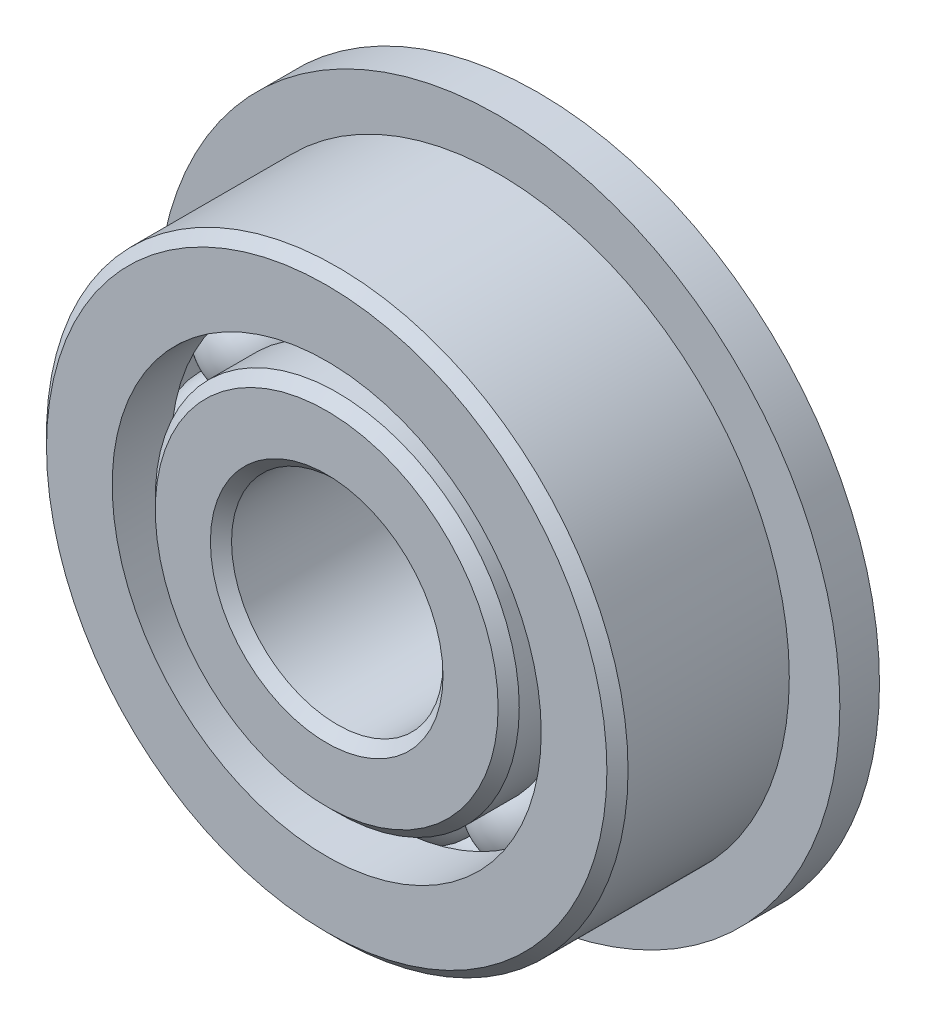
SolidWorks part; units mm, degrees
ref_plane "Front Plane" through (0, 0, 0) normal (0, 0, 1) x (1, 0, 0)
ref_plane "Top Plane" through (0, 0, 0) normal (0, 1, 0) x (1, 0, 0)
ref_plane "Right Plane" through (0, 0, 0) normal (1, 0, 0) x (0, 0, -1)
sketch "Sketch1" plane through (0, 0, 0) normal (1, 0, 0) x (0, 0, -1)
  line L0 (-3.175, 0) -> (3.175, 0) construction
  line L1 (0, 8.7312) -> (0, -8.7312) construction
  line L2 (2.8575, 8.7312) -> (-2.8575, 8.7312)
  line L3 (-2.8575, 8.7312) -> (-3.175, 8.4137)
  line L4 (-3.175, 8.4137) -> (-3.175, 6.4416)
  line L5 (-3.175, 6.4416) -> (-1.4111, 6.4416)
  line L6 (3.175, 6.4416) -> (1.4111, 6.4416)
  line L7 (3.175, 8.4137) -> (3.175, 6.4416)
  line L8 (2.8575, 8.7312) -> (3.175, 8.4137)
  line L9 (0, 8.7312) -> (0, 5.9531) construction
  line L10 (0, 5.9531) -> (0, 3.175) construction
  arc A0 (-1.4111, 6.4416) -> (1.4111, 6.4416) centre (0, 5.9531) cw
  point P14 (0, 3.175)
  dimension "Width" = 6.35
  dimension "OD" = 17.4625
  dimension "D1" = 45
  dimension "D2" = 0.3175
  dimension "D3" = 2.8222
  dimension "D4" = 0.4885
revolve "Revolve1" add sketch "Sketch1" angle 360 about L0
sketch "Sketch3" plane through (0, 0, 0) normal (1, 0, 0) x (0, 0, -1)
  line L0 (-1.4111, 5.4647) -> (-3.175, 5.4647) construction
  line L1 (-3.175, 8.4137) -> (-3.175, 6.4416) construction
  line L2 (-2.8575, 8.7312) -> (-3.175, 8.4137) construction
  line L3 (-3.175, 5.4647) -> (-3.175, 3.4925) construction
  line L4 (-3.175, 3.4925) -> (-3.175, 5.1472)
  line L5 (-3.175, 3.4925) -> (-2.8575, 3.175)
  line L6 (-2.8575, 3.175) -> (4.445, 3.175)
  line L7 (-3.175, 8.4137) -> (-3.175, -8.4137) construction
  line L8 (4.445, 3.175) -> (4.7625, 3.4925)
  line L10 (4.7625, 3.4925) -> (4.7625, 5.4647) construction
  line L11 (4.7625, 5.4647) -> (1.4111, 5.4647) construction
  line L12 (0, 8.7312) -> (0, -8.7312) construction
  line L13 (2.8575, 8.7312) -> (3.175, 8.4137) construction
  line L14 (-3.175, 5.1472) -> (-2.8575, 5.4647)
  line L15 (-2.8575, 5.4647) -> (-1.4111, 5.4647)
  line L16 (1.4111, 5.4647) -> (4.445, 5.4647)
  line L17 (4.445, 5.4647) -> (4.7625, 5.1472)
  line L18 (4.7625, 5.1472) -> (4.7625, 3.4925)
  arc A1 (1.4111, 5.4647) -> (-1.4111, 5.4647) centre (0, 5.9531) cw
  arc A2 (1.4111, 6.4416) -> (-1.4111, 6.4416) centre (0, 5.9531) ccw construction
  dimension "D1" = 45
  dimension "Ring Wd" = 7.9375
revolve "Revolve3" add sketch "Sketch3" angle 360 about L0
sketch "Sketch4" plane through (0, 0, 0) normal (1, 0, 0) x (0, 0, -1)
  line L0 (-1.4933, 5.9531) -> (1.4933, 5.9531)
  arc A2 (-1.4933, 5.9531) -> (1.4933, 5.9531) centre (0, 5.9531) cw
  arc A3 (1.4111, 6.4416) -> (-1.4111, 6.4416) centre (0, 5.9531) ccw construction
revolve "Revolve4" add sketch "Sketch4" angle 360 about L0
ref_axis "Axis1" through (0, 0, -3.175) along (0, 0, 1)
pattern_circular "CirPattern1" count 12 every 30 about axis through (0, 0, -3.175) along (0, 0, 1) of bodies 104
sketch "Sketch5" plane through (0, 0, 0) normal (1, 0, 0) x (0, 0, -1)
  line L0 (-3.175, 6.4416) -> (-1.4111, 6.4416) construction
  line L1 (-3.0163, 6.4416) -> (-1.4933, 6.4416)
  line L2 (-3.0163, 6.4416) -> (-3.0163, 5.4647)
  line L3 (-3.0163, 5.4647) -> (-1.4933, 5.4647)
  line L4 (-1.4933, 6.4416) -> (-1.4933, 5.4647)
  line L5 (-1.4111, 5.4647) -> (-3.175, 5.4647) construction
  line L6 (3.175, 6.4416) -> (1.4111, 6.4416) construction
  line L7 (3.0162, 6.4416) -> (1.4933, 6.4416)
  line L8 (3.0162, 6.4416) -> (3.0162, 5.4647)
  line L9 (3.0162, 5.4647) -> (1.4933, 5.4647)
  line L10 (1.4933, 6.4416) -> (1.4933, 5.4647)
  line L11 (4.7625, 5.4647) -> (1.4111, 5.4647) construction
  line L12 (-2.8575, 8.7312) -> (-3.175, 8.4137) construction
  point P18 (-3.0163, 8.5725)
revolve "Revolve5" [suppressed] add sketch "Sketch5" angle 360 about L0
sketch "Sketch6" plane through (0, 0, 0) normal (1, 0, 0) x (0, 0, -1)
  line L1 (3.175, 6.4416) -> (1.9844, 6.4416)
  line L2 (3.175, 6.4416) -> (3.175, 10.2489)
  line L3 (3.175, 10.2489) -> (1.9844, 10.2489)
  line L4 (1.9844, 6.4416) -> (1.9844, 10.2489)
  line L5 (3.175, 0) -> (-3.175, 0) construction
  dimension "Flange OD" = 20.4978
  dimension "Th" = 1.1906
revolve "Revolve6" add sketch "Sketch6" angle 360 about L5
equation "\"D2@Sketch1\" = \"Width@Sketch1\"*.05"
equation "\"D3@Sketch1\" = \"Width@Sketch1\"/2.25"
equation "\"D4@Sketch1\" = (((\"OD@Sketch1\"-\"Width@Sketch1\")/2)/3.25)/3.5"
equation "\"D2@CirPattern1\" = 360/\"Balls@CirPattern1\""
